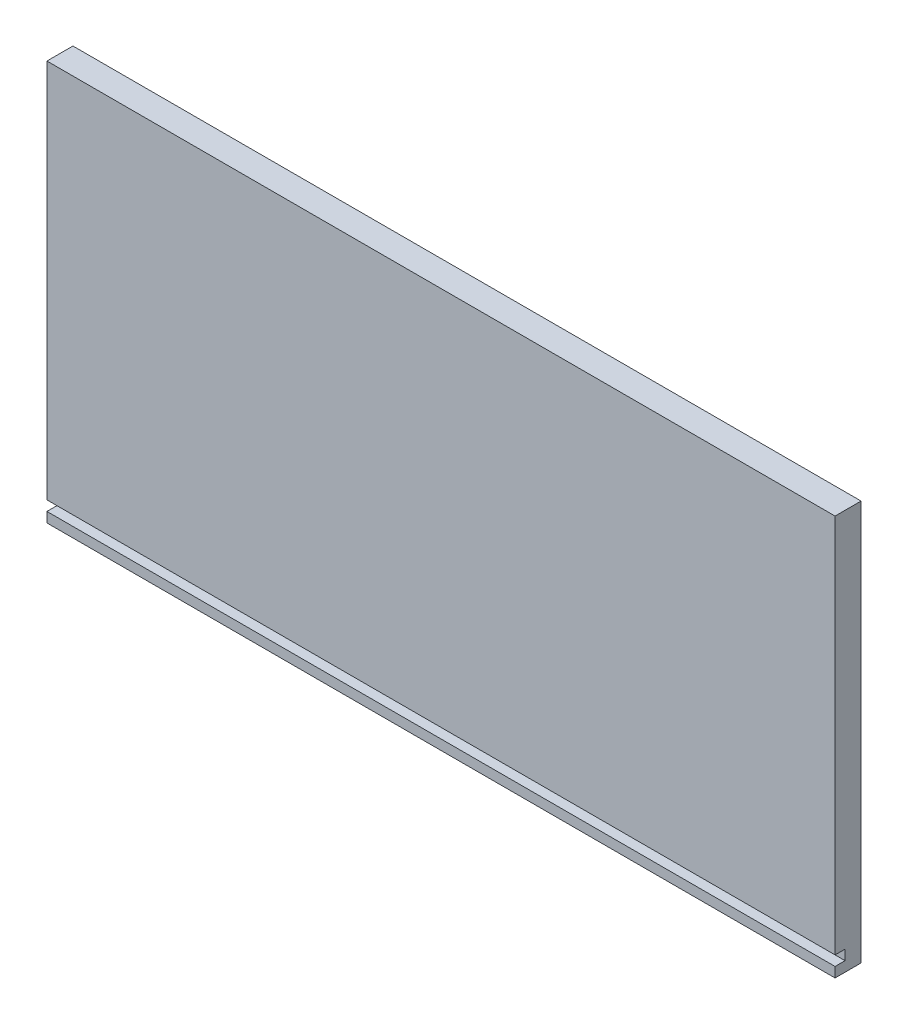
SolidWorks part; units mm, degrees
ref_plane "正面" through (0, 0, 0) normal (0, 0, 1) x (1, 0, 0)
ref_plane "平面" through (0, 0, 0) normal (0, 1, 0) x (1, 0, 0)
ref_plane "右側面" through (0, 0, 0) normal (1, 0, 0) x (0, 0, -1)
sketch "ｽｹｯﾁ1" plane through (0, 0, 0) normal (0, 0, 1) x (1, 0, 0)
  line L1 (-69.2801, 161.5071) -> (324.7199, 161.5071)
  line L2 (-69.2801, 161.5071) -> (-69.2801, -38.4929)
  line L3 (-69.2801, -38.4929) -> (324.7199, -38.4929)
  line L4 (324.7199, 161.5071) -> (324.7199, -38.4929)
  dimension "D1" = 394
  dimension "D3" = 200
extrude "ﾎﾞｽ - 押し出し1" add sketch "ｽｹｯﾁ1" along normal blind 13
sketch "ｽｹｯﾁ2" plane through (0, 0, 13) normal (0, 0, 1) x (1, 0, 0)
  line L0 (324.7199, -38.4929) -> (324.7199, 161.5071) construction
  line L1 (324.7199, -33.4929) -> (-69.2801, -33.4929)
  line L2 (324.7199, -33.4929) -> (324.7199, -28.4929)
  line L3 (324.7199, -28.4929) -> (-69.2801, -28.4929)
  line L4 (-69.2801, -33.4929) -> (-69.2801, -28.4929)
  line L5 (-69.2801, 161.5071) -> (-69.2801, -38.4929) construction
  line L7 (-69.2801, -38.4929) -> (324.7199, -38.4929) construction
  dimension "D1" = 5
  dimension "D2" = 394
  dimension "D3" = 5
extrude "ｶｯﾄ - 押し出し1" cut sketch "ｽｹｯﾁ2" against normal blind 5
